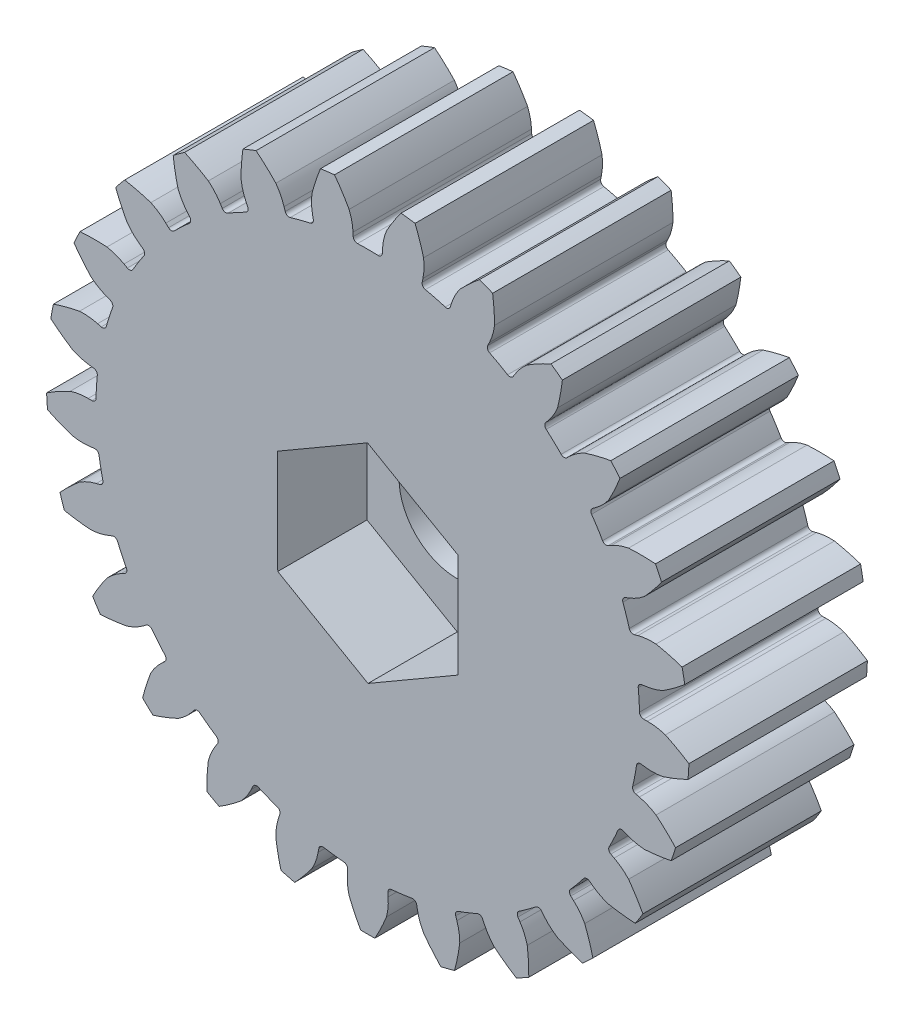
SolidWorks part; units mm, degrees
ref_plane "Plano frontal" through (0, 0, 0) normal (0, 0, 1) x (1, 0, 0)
ref_plane "Plano superior" through (0, 0, 0) normal (0, 1, 0) x (1, 0, 0)
ref_plane "Plano direito" through (0, 0, 0) normal (1, 0, 0) x (0, 0, -1)
sketch "Esboço1" plane through (0, 0, -10.2037) normal (0, 0, 1) x (1, 0, 0)
  circle A0 centre (175.26, 0) radius 7.14
  circle A1 centre (175.26, 0) radius 18.009
  circle A2 centre (175.26, 0) radius 7.14 construction
  circle A3 centre (175.26, 0) radius 7.14 construction
  dimension "D1" = 36.018
extrude "Ressalto-extrusão1" add sketch "Esboço1" against normal up to surface (5 mm away) contours A0
extrude "Ressalto-extrusão2" add sketch "Esboço1<3>" along normal up to surface (10 mm away) contours A1
sketch "Esboço1<3>" plane through (0, 0, -10.2037) normal (0, 0, 1) x (1, 0, 0) same geometry as "Esboço1"
sketch "Esboço2" plane through (0, 0, -0.2037) normal (0, 0, 1) x (1, 0, 0)
  circle A0 centre (175.26, 0) radius 3.25
  dimension "D1" = 6.5
extrude "Corte-extrusão1" cut sketch "Esboço2" against normal through all
sketch "Esboço3" plane through (0, 0, -0.2037) normal (0, 0, 1) x (1, 0, 0)
  line L0 (175.26, 0) -> (175.26, 18.009) construction
  line L2 (176.0742, 15.4373) -> (176.0853, 15.6478)
  line L3 (177.1229, 17.9124) -> (168.9885, 14.3597) construction
  line L4 (174.4347, 15.6478) -> (174.4458, 15.4373)
  line L5 (176.2509, 16.7701) -> (172.1791, 16.5144) construction
  line L6 (174.215, 16.6422) -> (171.6062, 16.2698) construction
  line L7 (176.305, 16.6422) -> (174.215, 16.6422) construction
  circle A0 centre (175.26, 0) radius 15.2305 construction
  circle A1 centre (175.26, 0) radius 15.6695 construction
  circle A2 centre (175.26, 0) radius 16.675 construction
  circle A3 centre (175.26, 0) radius 18.009 construction
  arc A4 (174.4347, 15.6478) -> (174.215, 16.6422) centre (171.3347, 15.4843) ccw
  arc A5 (174.215, 16.6422) -> (173.3971, 17.9124) centre (164.1757, 11.0757) ccw
  arc A6 (176.0853, 15.6478) -> (176.305, 16.6422) centre (179.1853, 15.4843) cw
  arc A7 (176.305, 16.6422) -> (177.1229, 17.9124) centre (186.3443, 11.0757) cw
  arc A8 (174.6842, 15.2196) -> (175.8358, 15.2196) centre (175.26, 0) cw
  arc A10 (174.6842, 15.2196) -> (174.4458, 15.4373) centre (174.6755, 15.4494) cw
  arc A11 (175.8358, 15.2196) -> (176.0742, 15.4373) centre (175.8445, 15.4494) ccw
  arc A12 (173.3971, 17.9124) -> (177.1229, 17.9124) centre (175.26, -0.0001) cw
  point P38 (174.4579, 15.2094)
  point P41 (176.0621, 15.2094)
  dimension "D1" = 30.461
  dimension "D2" = 33.35
  dimension "D3" = 31.339
  dimension "D5" = 3.1043
  dimension "D6" = 0.23
  dimension "D7" = 20
  dimension "D4" = 2.09
extrude "Corte-extrusão2" cut sketch "Esboço3" against normal blind 10
pattern_circular "PadrãoCircular1" count 25 over 360 about axis through (175.26, 0, -0.2037) along (0, 0, -1) of "Corte-extrusão2"
sketch "Esboço4" plane through (0, 0, -0.2037) normal (0, 0, 1) x (1, 0, 0)
  line L1 (175.2467, 5.8312) -> (170.2034, 2.9041)
  line L2 (170.2034, 2.9041) -> (170.2167, -2.9271)
  line L3 (170.2167, -2.9271) -> (175.2733, -5.8312)
  line L4 (175.2733, -5.8312) -> (180.3166, -2.9041)
  line L5 (180.3166, -2.9041) -> (180.3033, 2.9271)
  line L6 (180.3033, 2.9271) -> (175.2467, 5.8312)
  circle A0 centre (175.26, 0) radius 5.05 construction
  dimension "D1" = 10.1
extrude "Corte-extrusão3" cut sketch "Esboço4" against normal blind 5
